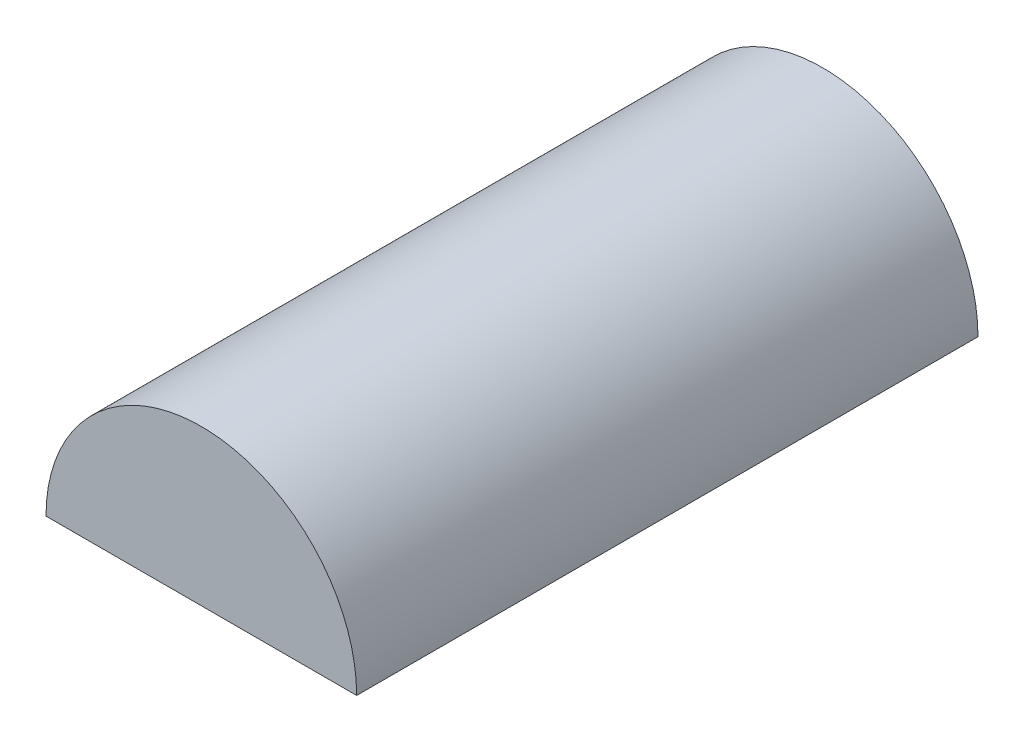
SolidWorks part; units mm, degrees
ref_plane "Front Plane" through (0, 0, 0) normal (0, 0, 1) x (1, 0, 0)
ref_plane "Top Plane" through (0, 0, 0) normal (0, 1, 0) x (1, 0, 0)
ref_plane "Right Plane" through (0, 0, 0) normal (1, 0, 0) x (0, 0, -1)
sketch "Sketch1" plane through (0, 0, 0) normal (0, 0, 1) x (1, 0, 0)
  line L0 (-101.6, 0) -> (101.6, 0)
  arc A0 (-101.6, 0) -> (101.6, 0) centre (0, 0) cw
  dimension "D1" = 101.6
extrude "Boss-Extrude1" add sketch "Sketch1" along normal blind 406.4
shell "Shell1" thickness 6.35 removed face at (0, 0, 203.2)
